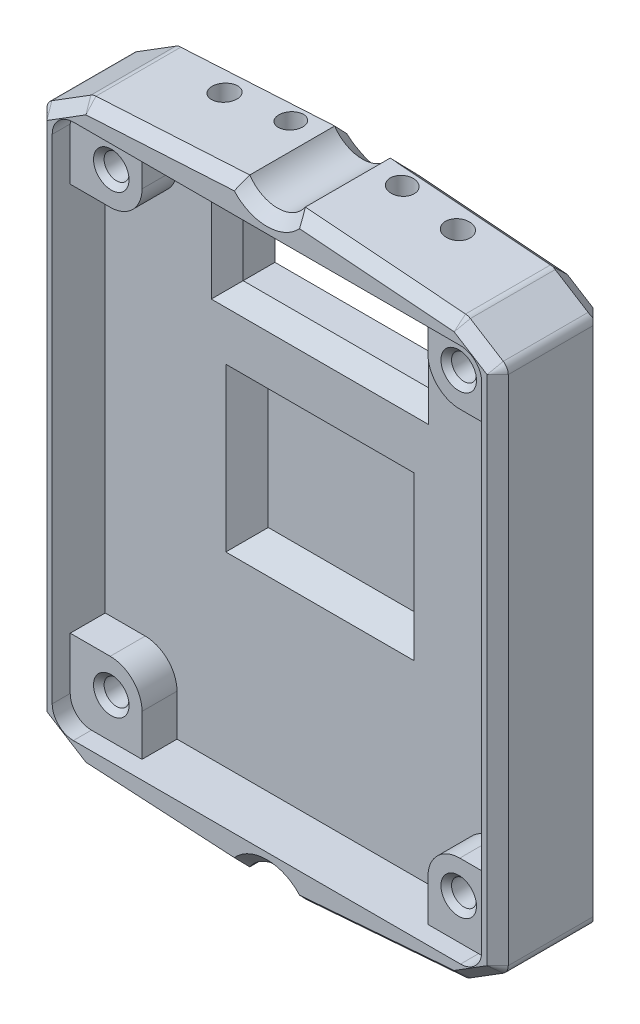
SolidWorks part; units mm, degrees
ref_plane "Front Plane" through (0, 0, 0) normal (0, 0, 1) x (1, 0, 0)
ref_plane "Top Plane" through (0, 0, 0) normal (0, 1, 0) x (1, 0, 0)
ref_plane "Right Plane" through (0, 0, 0) normal (1, 0, 0) x (0, 0, -1)
sketch "Sketch1" plane through (0, 0, 0) normal (0, 0, 1) x (1, 0, 0)
  line L0 (-23.25, 28.25) -> (-23.25, -28.25)
  line L1 (-20.25, 25.25) -> (20.25, 25.25)
  line L2 (-20.25, 25.25) -> (-20.25, -25.25)
  line L3 (-20.25, -25.25) -> (20.25, -25.25)
  line L4 (20.25, 25.25) -> (20.25, -25.25)
  line L5 (-20.25, 25.25) -> (20.25, -25.25) construction
  line L6 (-20.25, -25.25) -> (20.25, 25.25) construction
  line L7 (-23.25, -28.25) -> (23.25, -28.25)
  line L8 (23.25, 28.25) -> (23.25, -28.25)
  line L9 (-23.25, 28.25) -> (23.25, 28.25)
  point P0 (0, 0)
  dimension "D1" = 50.5
  dimension "D2" = 40.5
  dimension "D3" = 3
extrude "Boss-Extrude1" add sketch "Sketch1" along normal blind 5
sketch "Sketch2" plane through (0, 0, 0) normal (0, 0, -1) x (-1, 0, 0)
  line L1 (-23.25, 28.25) -> (23.25, 28.25)
  line L2 (-23.25, 28.25) -> (-23.25, -28.25)
  line L3 (-23.25, -28.25) -> (23.25, -28.25)
  line L4 (23.25, 28.25) -> (23.25, -28.25)
extrude "Boss-Extrude2" add sketch "Sketch2" along normal blind 6
sketch "Sketch3" plane through (0, 0, 0) normal (0, 0, 1) x (1, 0, 0)
  line L0 (0, 0) -> (0, 30.8352) construction
  line L1 (0, 0) -> (-31.9704, 0) construction
  line L2 (-20.25, 25.25) -> (-20.25, 18.3322)
  line L3 (-20.25, 25.25) -> (-20.25, -25.25) construction
  line L4 (-20.25, 18.3322) -> (-13.4806, 18.3322)
  line L5 (-13.4806, 18.3322) -> (-13.4806, 25.25)
  line L6 (20.25, 25.25) -> (-20.25, 25.25) construction
  line L7 (-13.4806, 25.25) -> (-20.25, 25.25)
  line L8 (13.4806, 25.25) -> (20.25, 25.25)
  line L9 (13.4806, 18.3322) -> (13.4806, 25.25)
  line L10 (20.25, 18.3322) -> (13.4806, 18.3322)
  line L11 (20.25, 25.25) -> (20.25, 18.3322)
  line L12 (20.25, -25.25) -> (20.25, -18.3322)
  line L13 (20.25, -18.3322) -> (13.4806, -18.3322)
  line L14 (13.4806, -18.3322) -> (13.4806, -25.25)
  line L15 (13.4806, -25.25) -> (20.25, -25.25)
  line L16 (-13.4806, -25.25) -> (-20.25, -25.25)
  line L17 (-13.4806, -18.3322) -> (-13.4806, -25.25)
  line L18 (-20.25, -18.3322) -> (-13.4806, -18.3322)
  line L19 (-20.25, -25.25) -> (-20.25, -18.3322)
  circle A0 centre (-16.38, 21.46) radius 1.175
  circle A1 centre (16.38, 21.46) radius 1.175
  circle A2 centre (16.38, -21.46) radius 1.175
  circle A3 centre (-16.38, -21.46) radius 1.175
  dimension "D3" = 2.35
  dimension "D1" = 21.46
  dimension "D2" = 16.38
extrude "Boss-Extrude3" add sketch "Sketch3" along normal blind 3.3
chamfer "Chamfer3" distance 4.5 angle 58 4 edges at (-23.25, -28.25, -0.5) (23.25, -28.25, -0.5) (-23.25, 28.25, -0.5) (23.25, 28.25, -0.5) first distance on face at (-23.25, 0, -0.5) first distance on face at (23.25, 0, -0.5)
fillet "Fillet1" radius 3 4 edges at (13.4806, -18.3322, 1.65) (-13.4806, -18.3322, 1.65) (13.4806, 18.3322, 1.65) (-13.4806, 18.3322, 1.65)
sketch "Sketch4" plane through (0, 0, 0) normal (0, 0, 1) x (1, 0, 0)
  line L0 (20.25, 25.25) -> (-20.25, 25.25) construction
  line L1 (-8.75, 23.8) -> (8.75, 23.8)
  line L2 (-8.75, 23.8) -> (-8.75, 13.8)
  line L3 (-8.75, 13.8) -> (8.75, 13.8)
  line L4 (8.75, 23.8) -> (8.75, 13.8)
  point P4 (0, 13.8)
  dimension "D1" = 10
  dimension "D2" = 1.45
  dimension "D3" = 17.5
extrude "Cut-Extrude1" cut sketch "Sketch4" against normal through all
sketch "Sketch5" plane through (0, 0, -6) normal (0, 0, -1) x (-1, 0, 0)
  line L0 (-29.5901, 0) -> (35.962, 0) construction
  line L4 (0, 42.4173) -> (0, 14.6256) construction
  line L8 (-23.25, -28.25) -> (23.25, -28.25)
  line L9 (23.25, -28.25) -> (23.25, -27.0847)
  line L10 (23.25, -27.0847) -> (2.6192, -28.25)
  line L11 (-23.25, -26.638) -> (-2.6192, -28.25)
  line L12 (-23.25, -28.25) -> (-23.25, -26.638)
  line L14 (16.0485, 28.25) -> (-16.0485, 28.25) construction
  line L15 (-2.6192, 28.25) -> (2.6192, 28.25)
  line L16 (-23.25, 28.25) -> (-23.25, 26.638)
  line L17 (-23.25, 26.638) -> (-2.6192, 28.25)
  line L18 (23.25, 27.0847) -> (2.6192, 28.25)
  line L19 (23.25, 28.25) -> (23.25, 27.0847)
  line L20 (-23.25, 28.25) -> (23.25, 28.25)
  arc A0 (-2.6192, 28.25) -> (2.6192, 28.25) centre (0, 30) ccw
  arc A1 (-2.6192, -28.25) -> (2.6192, -28.25) centre (0, -30) cw
  line M10 (-16.0485, -28.25) -> (16.0485, -28.25)
  line M12 (16.0485, 28.25) -> (-16.0485, 28.25)
  line M22 (16.0485, -28.25) -> (23.25, -23.75)
  line M23 (23.25, 23.75) -> (16.0485, 28.25)
  line M24 (-16.0485, 28.25) -> (-23.25, 23.75)
  line M25 (-23.25, -23.75) -> (-16.0485, -28.25)
  dimension "D1" = 6.3
  dimension "D3" = 60
extrude "Cut-Extrude2" cut sketch "Sketch5" against normal through all contours L12 L8 L11 M25 | A1 L8 | L9 L10 L8 M22 | L11 M25 M10 | L10 L8 M22 | L17 M24 M12 | L18 M23 M12 | L20 L18 L19 M23 | L20 L16 L17 M24 | A0 M12 | L11 A1 L10 L9 L8 L12 region at (20.2805, -27.5835, -6) region at (-12.0169, -27.972, -6) region at (0, -27.6777, -6) region at (12.2118, -27.8502, -6) region at (-20.1718, -27.7652, -6) region at (-12.0169, 27.972, -6) region at (12.2118, 27.8502, -6) region at (0, 27.6777, -6) region at (20.2805, 27.5835, -6) region at (-20.1718, 27.7652, -6)
sketch "Sketch6" plane through (0, 0, 5) normal (0, 0, 1) x (1, 0, 0)
  line L0 (-17.3831, -27.4161) -> (-2.6192, -28.25) construction
  line L1 (-23.2503, 33.2078) -> (-21.7503, 33.2078)
  line L2 (-23.2503, 33.2078) -> (-23.2503, -27.1694)
  line L3 (-23.2503, -27.1694) -> (-21.7503, -27.1694)
  line L4 (-21.7503, 33.2078) -> (-21.7503, -27.1694)
  line L5 (0, 0) -> (0, 31.5361) construction
  line L6 (21.7503, 33.2078) -> (21.7503, -27.1694)
  line L7 (23.2503, -27.1694) -> (21.7503, -27.1694)
  line L8 (23.2503, 33.2078) -> (23.2503, -27.1694)
  line L9 (23.2503, 33.2078) -> (21.7503, 33.2078)
  dimension "D1" = 1.5
extrude "Cut-Extrude3" cut sketch "Sketch6" against normal through all
sketch "Sketch7" plane through (0, 0, 0) normal (0, 1, 0) x (1, 0, 0)
  line L0 (-5.25, 2.5) -> (5.25, 2.5) construction
  line L1 (2.6192, 6) -> (-2.6192, 6) construction
  circle A0 centre (-5.25, 2.5) radius 1.125
  circle A1 centre (5.25, 2.5) radius 1.125
  point P4 (0, 2.5)
  dimension "D1" = 2.25
  dimension "D2" = 10.5
  dimension "D3" = 3.5
extrude "Cut-Extrude4" cut sketch "Sketch7" against normal blind 10 from offset 30
mirror "Mirror1" about plane through (0, 0, 0) normal (0, 1, 0) of "Cut-Extrude4"
chamfer "Chamfer6" distance 2 angle 45 12 edges at (19.859, -25.8689, -6) (10.2934, -27.6504, -6) (0, -26.85, -6) (-10.0011, -27.833, -6) (-19.5667, -26.0516, -6) (-21.7503, 0, -6) (-19.5667, 26.0516, -6) (21.7503, 0, -6) (19.859, 25.8689, -6) (-10.0011, 27.833, -6) (0, 26.85, -6) (10.2934, 27.6504, -6)
fillet "Fillet2" radius 1 8 edges at (21.7503, -24.6871, 0.5) (17.9677, -27.0507, 0.5) (-17.3831, -27.4161, 0.5) (-21.7503, -24.6871, 0.5) (-21.7503, 24.6871, 0.5) (21.7503, 24.6871, 0.5) (-17.3831, 27.4161, 0.5) (17.9677, 27.0507, 0.5)
chamfer "Chamfer1" distance 1 angle 45 20 edges at (0, -26.85, 5) (0, 26.85, 5) (-9.8731, -27.8403, 5) (-21.7503, 0, 5) (10.1713, -27.6599, 5) (21.7503, 0, 5) (-17.3733, -27.3852, 5) (-19.4404, -26.1305, 5) (-19.4404, 26.1305, 5) (-21.6249, -24.6176, 5) (-21.6249, 24.6176, 5) (17.9585, -27.0226, 5) (19.7279, 25.9509, 5) (19.7279, -25.9509, 5) (21.6249, 24.6176, 5) (21.6249, -24.6176, 5) (-9.8731, 27.8403, 5) (-17.3733, 27.3852, 5) (10.1713, 27.6599, 5) (17.9585, 27.0226, 5)
fillet "Fillet3" radius 2 4 edges at (-20.25, -25.25, 3.8088) (20.25, -25.25, 3.8088) (20.25, 25.25, 3.8088) (-20.25, 25.25, 3.8088)
sketch "Sketch8" plane through (0, 0, 3.3) normal (0, 0, 1) x (1, 0, 0)
  circle A0 centre (-16.38, 21.46) radius 1.175
  circle A1 centre (16.38, 21.46) radius 1.175
  circle A2 centre (16.38, -21.46) radius 1.175
  circle A3 centre (-16.38, -21.46) radius 1.175
  circle A4 centre (-16.38, 21.46) radius 1.175 construction
extrude "Cut-Extrude5" cut sketch "Sketch8" against normal through all
sketch "Sketch9" plane through (0, 0, -6) normal (0, 0, -1) x (-1, 0, 0)
  line L0 (0, 9.9819) -> (0, -23.9909) construction
  line L1 (-16.3742, -2.0365) -> (-6.3848, -2.0365)
  line L2 (-12.6187, -3.5365) -> (-6.3848, -3.5365)
  line L3 (-16.3742, -2.0365) -> (0, -17.5995)
  line L4 (-12.6187, -3.5365) -> (0, -15.5301)
  line L5 (-4, -2.7865) -> (-12.6323, -2.7865) construction
  line L6 (12.6187, -3.5365) -> (0, -15.5301)
  line L7 (16.3742, -2.0365) -> (0, -17.5995)
  line L8 (12.6187, -3.5365) -> (6.3848, -3.5365)
  line L9 (16.3742, -2.0365) -> (6.3848, -2.0365)
  arc A0 (-6.3848, -3.5365) -> (-6.3848, -2.0365) centre (-4, -2.7865) ccw
  arc A1 (6.3848, -3.5365) -> (6.3848, -2.0365) centre (4, -2.7865) cw
  dimension "D1" = 5
  dimension "D2" = 1.5
  dimension "D3" = 1.5
  dimension "D4" = 8
extrude "Cut-Extrude6" cut sketch "Sketch9" against normal blind 1
chamfer "Chamfer2" distance 0.5 angle 45 4 edges at (-17.555, -21.46, 3.3) (17.555, -21.46, 3.3) (15.205, 21.46, 3.3) (-15.205, 21.46, 3.3)
chamfer "Chamfer4" distance 1 angle 45 10 edges at (-8.1871, -9.818, -6) (-11.3795, -2.0365, -6) (-1.5, -2.7865, -6) (-9.5018, -3.5365, -6) (-6.3093, -9.5333, -6) (6.3093, -9.5333, -6) (9.5018, -3.5365, -6) (1.5, -2.7865, -6) (11.3795, -2.0365, -6) (8.1871, -9.818, -6)
sketch "Sketch10" plane through (0, 0, 0) normal (0, 1, 0) x (1, 0, 0)
  line L0 (-11, 2) -> (11, 2) construction
  circle A0 centre (-11, 2) radius 1.175
  circle A1 centre (11, 2) radius 1.175
  point P4 (0, 2)
  dimension "D1" = 2.35
  dimension "D2" = 22
  dimension "D3" = 2
extrude "Cut-Extrude7" cut sketch "Sketch10" against normal through all both and the other way through all
sketch "Sketch11" plane through (0, 0, 0) normal (0, 0, 1) x (1, 0, 0)
  line L1 (-8.8805, 7.6666) -> (8.8805, 7.6666)
  line L2 (-8.8805, 7.6666) -> (-8.8805, -7.6666)
  line L3 (-8.8805, -7.6666) -> (8.8805, -7.6666)
  line L4 (8.8805, 7.6666) -> (8.8805, -7.6666)
  line L5 (-8.8805, 7.6666) -> (8.8805, -7.6666) construction
  line L6 (-8.8805, -7.6666) -> (8.8805, 7.6666) construction
  point P0 (0, 0)
extrude "Cut-Extrude8" cut sketch "Sketch11" against normal blind 2
chamfer "Chamfer5" distance 2 angle 45 4 edges at (0, -7.6666, -2) (-8.8805, 0, -2) (0, 7.6666, -2) (8.8805, 0, -2)
chamfer "Chamfer7" distance 1.5 angle 45 8 edges at (8.75, 18.8, 0) (0, 23.8, 0) (-8.75, 18.8, 0) (0, 13.8, 0) (-8.75, 18.8, -6) (0, 23.8, -6) (8.75, 18.8, -6) (0, 13.8, -6)
